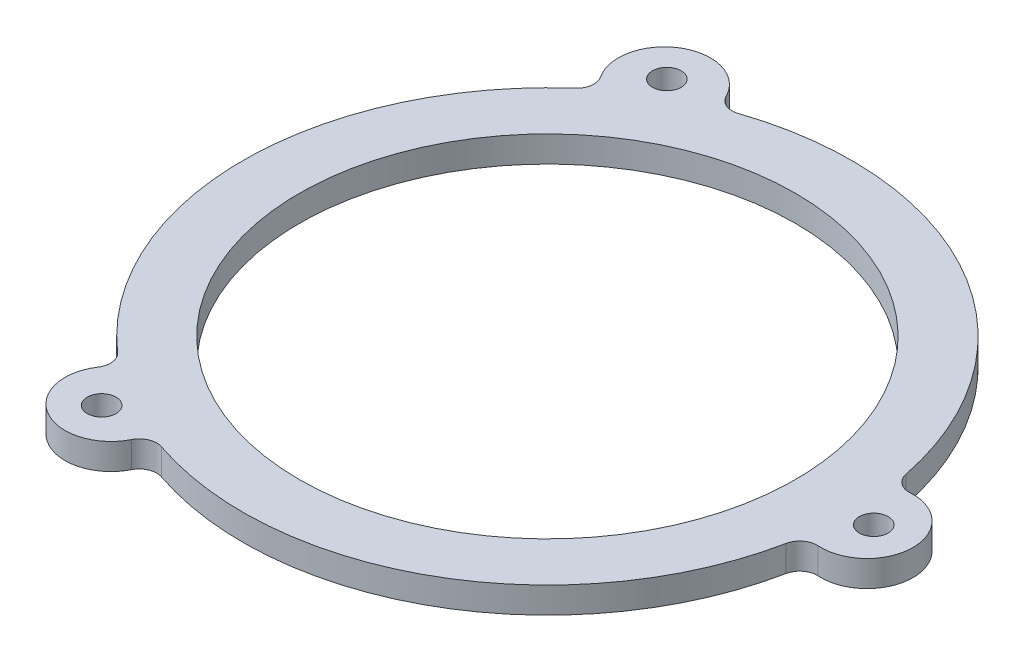
SolidWorks part; units mm, degrees
ref_plane "Front Plane" through (0, 0, 0) normal (0, 0, 1) x (1, 0, 0)
ref_plane "Top Plane" through (0, 0, 0) normal (0, 1, 0) x (1, 0, 0)
ref_plane "Right Plane" through (0, 0, 0) normal (1, 0, 0) x (0, 0, -1)
sketch "Sketch1" plane through (0, 0, 0) normal (0, 1, 0) x (1, 0, 0)
  circle A0 centre (0, 0) radius 28.5
  circle A1 centre (0, 0) radius 35
  dimension "D1" = 57
  dimension "D2" = 70
extrude "Boss-Extrude1" add sketch "Sketch1" along normal blind 3
sketch "Sketch3" plane through (0, 3, 0) normal (0, 1, 0) x (1, 0, 0)
  line L1 (0, 0) -> (42, 0) construction
  line L2 (0, 0) -> (34.6594, -4.8711) construction
  line L3 (0, 0) -> (34.6594, 4.8711) construction
  line L4 (0, 0) -> (-21, -36.3731) construction
  line L5 (0, 0) -> (-21, 36.3731) construction
  line L6 (0, 0) -> (-13.1112, -32.4514) construction
  line L7 (0, 0) -> (-21.5482, -27.5804) construction
  line L8 (0, 0) -> (-13.1112, 32.4514) construction
  line L9 (0, 0) -> (-21.5482, 27.5804) construction
  circle A4 centre (0, 0) radius 35 construction
  arc A5 (34.6594, 4.8711) -> (34.6594, -4.8711) centre (0, 0) cw
  arc A6 (34.6594, 4.8711) -> (34.6594, -4.8711) centre (36.7267, 0) cw
  arc A7 (-13.1112, -32.4514) -> (-21.5482, -27.5804) centre (0, 0) cw
  arc A8 (-21.5482, -27.5804) -> (-13.1112, -32.4514) centre (-18.3562, -31.7938) ccw
  arc A9 (-13.1112, 32.4514) -> (-21.5482, 27.5804) centre (0, 0) ccw
  arc A10 (-13.1112, 32.4514) -> (-21.5482, 27.5804) centre (-18.3603, 31.801) ccw
  dimension "D1" = 8
  dimension "D2" = 8
  dimension "D3" = 120
  dimension "D4" = 120
  dimension "D5" = 8
  dimension "D6" = 8
  dimension "D7" = 8
  dimension "D8" = 8
extrude "Boss-Extrude2" add sketch "Sketch3" against normal blind 3
fillet "Fillet1" radius 2 6 edges at (-13.1112, 1.5, -32.4514) (-21.5482, 1.5, -27.5804) (-21.5482, 1.5, 27.5804) (-13.1112, 1.5, 32.4514) (34.6594, 1.5, 4.8711) (34.6594, 1.5, -4.8711)
sketch "Sketch6" plane through (0, 3, 0) normal (0, 1, 0) x (1, 0, 0)
  line L0 (0, 0) -> (37.5, 0) construction
  line L1 (0, 0) -> (-18.75, -32.476) construction
  line L2 (0, 0) -> (-18.75, 32.476) construction
  circle A0 centre (37.5, 0) radius 1.65
  circle A1 centre (-18.75, -32.476) radius 1.65
  circle A2 centre (-18.75, 32.476) radius 1.65
  dimension "D1" = 3.3
extrude "Cut-Extrude2" cut sketch "Sketch6" against normal blind 10
